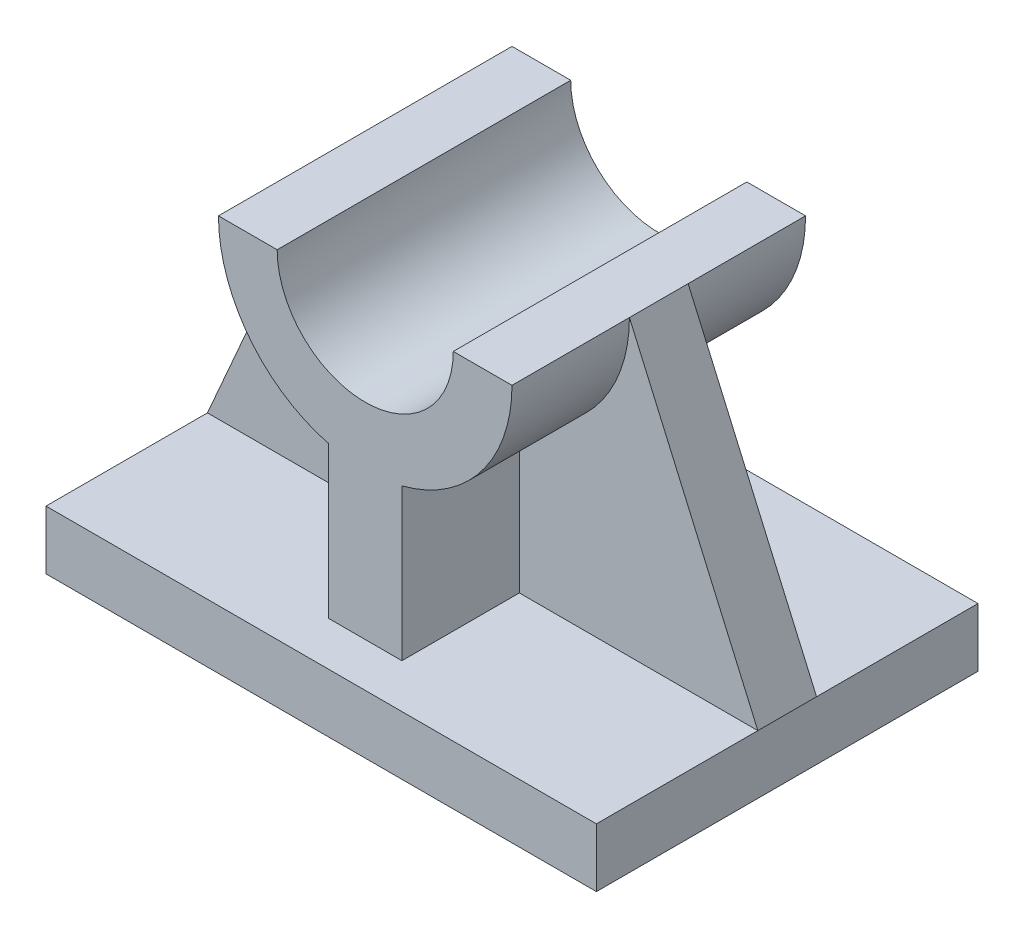
SolidWorks part; units mm, degrees
ref_plane "Front Plane" through (0, 0, 0) normal (0, 0, 1) x (1, 0, 0)
ref_plane "Top Plane" through (0, 0, 0) normal (0, 1, 0) x (1, 0, 0)
ref_plane "Right Plane" through (0, 0, 0) normal (1, 0, 0) x (0, 0, -1)
sketch "Sketch1" plane through (0, 0, 0) normal (0, 0, 1) x (1, 0, 0)
  line L0 (0, 0) -> (28697.5571, 0) construction
  line L1 (0, 0) -> (0, 28697.5571) construction
  line L2 (20, 48) -> (37.5, 8)
  line L7 (-37.5, 0) -> (37.5, 0)
  line L8 (-37.5, 0) -> (-37.5, 8)
  line L9 (-37.5, 8) -> (37.5, 8)
  line L10 (37.5, 0) -> (37.5, 8)
  line L11 (-20, 48) -> (-37.5, 8)
  line L12 (-20, 48) -> (-12, 48)
  line L13 (12, 48) -> (20, 48)
  line L14 (5, 28.6351) -> (5, 8)
  line L15 (-5, 28.6351) -> (-5, 8)
  arc A0 (-12, 48) -> (12, 48) centre (0, 48) ccw
  arc A1 (-20, 48) -> (-5, 28.6351) centre (0, 48) ccw
  arc A2 (5, 28.6351) -> (20, 48) centre (0, 48) ccw
  point P5 (-37.5, 0)
  point P13 (0, 8)
  dimension "D3" = 40
  dimension "D4" = 24
  dimension "D1" = 75
  dimension "D2" = 8
  dimension "D5" = 40
  dimension "D6" = 10
extrude "Boss-Extrude1" add sketch "Sketch1" along normal mid plane 52 contours L7 L10 L9 L8 region at (0, 4, 0)
extrude "Boss-Extrude2" add sketch "Sketch1<3>" along normal mid plane 40 contours L14 A2 L13 A0 L12 A1 L15 L9 region at (0, 31.0809, 0)
sketch "Sketch1<3>" plane through (0, 0, 0) normal (0, 0, 1) x (1, 0, 0) same geometry as "Sketch1"
extrude "Boss-Extrude3" add sketch "Sketch1<4>" along normal mid plane 8 contours A1 L11 L9 L15 | A2 L14 L9 L2 region at (19.2178, 21.2633, 0) region at (-19.2178, 21.2633, 0)
sketch "Sketch1<4>" plane through (0, 0, 0) normal (0, 0, 1) x (1, 0, 0) same geometry as "Sketch1"
